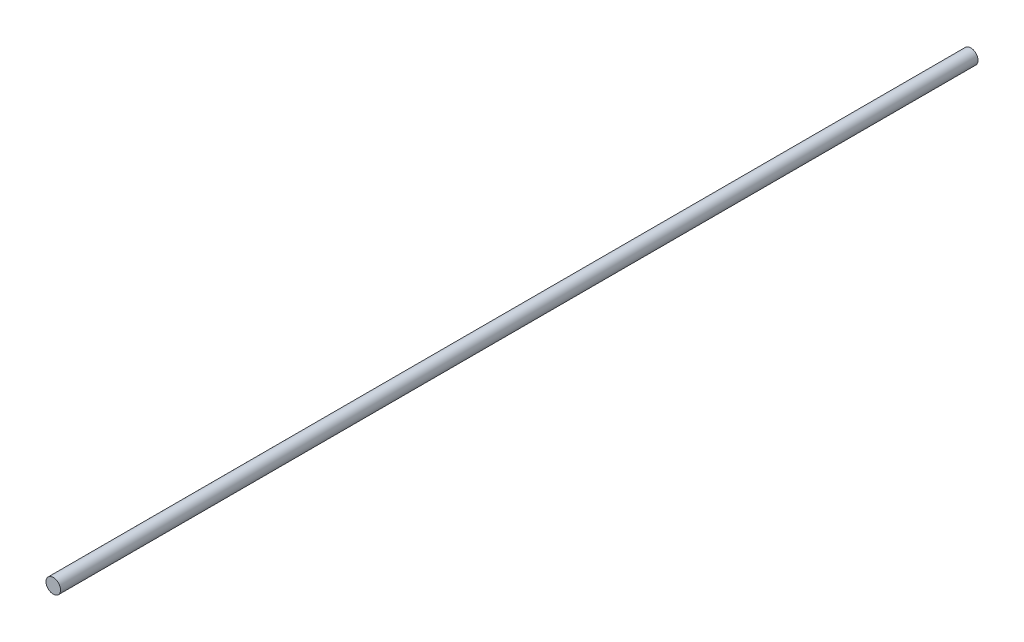
SolidWorks part; units mm, degrees
ref_plane "Front Plane" through (0, 0, 0) normal (0, 0, 1) x (1, 0, 0)
ref_plane "Top Plane" through (0, 0, 0) normal (0, 1, 0) x (1, 0, 0)
ref_plane "Right Plane" through (0, 0, 0) normal (1, 0, 0) x (0, 0, -1)
sketch3d "3DSketch1"
  circle A0 centre (0, 0, 0) radius 2.3813
  point P3 (0, 0, 2.3813)
ref_plane "Plane1" through (0, 0, 0) normal (0, 0, -1) x (-1, 0, 0)
extrude "Boss-Extrude1" add sketch "3DSketch1" along direction (0, 0, -1) on the side against the normal blind 300
